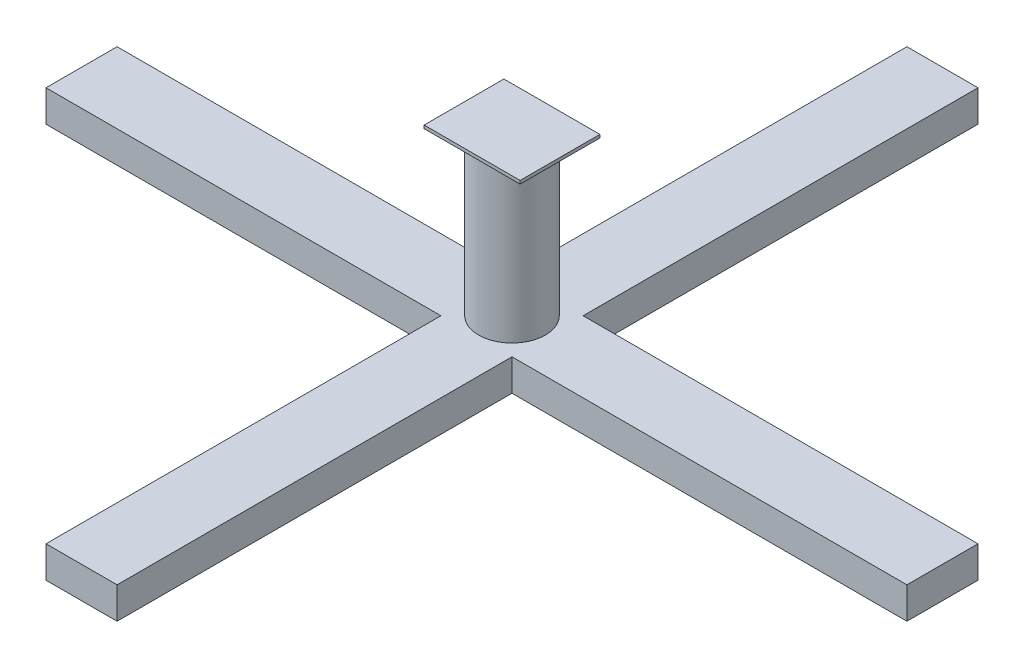
SolidWorks part; units mm, degrees
ref_plane "Alzado" through (0, 0, 0) normal (0, 0, 1) x (1, 0, 0)
ref_plane "Planta" through (0, 0, 0) normal (0, 1, 0) x (1, 0, 0)
ref_plane "Vista lateral" through (0, 0, 0) normal (1, 0, 0) x (0, 0, -1)
sketch "Croquis1" plane through (0, 0, 0) normal (0, 1, 0) x (1, 0, 0)
  line L0 (45, 0) -> (545, 0)
  line L1 (-45, 0) -> (-545, 0)
  line L2 (0, 45) -> (-545, 45)
  line L3 (-545, 0) -> (-545, 45)
  line L4 (0, 45) -> (545, 45)
  line L5 (545, 45) -> (545, 0)
  line L6 (0, -45) -> (545, -45)
  line L7 (545, -45) -> (545, 0)
  line L8 (0, -45) -> (-545, -45)
  line L9 (-545, -45) -> (-545, 0)
  line L10 (0, -45) -> (0, -545)
  line L11 (-45, 0) -> (-45, -545)
  line L12 (-45, -545) -> (0, -545)
  line L13 (45, 0) -> (45, -545)
  line L14 (45, -545) -> (0, -545)
  line L15 (0, 45) -> (0, 545)
  line L16 (-45, 0) -> (-45, 545)
  line L17 (-45, 545) -> (0, 545)
  line L18 (45, 0) -> (45, 545)
  line L19 (45, 545) -> (0, 545)
  circle A0 centre (0, 0) radius 45
  dimension "D1" = 90
  dimension "D2" = 500
  dimension "D3" = 500
  dimension "D4" = 500
  dimension "D5" = 500
extrude "Saliente-Extruir1" add sketch "Croquis1" along normal blind 40 contours L14 L13 L6 L10 | L11 L12 L10 L8 | L0 L13 L6 L7 | L18 L0 L5 L4 | L1 L16 L2 L3 | L11 L1 L9 L8 | A0 L11 L8 | A0 L18 L4 | A0 L2 L16 | L17 L16 L2 L15 | L18 L19 L15 L4 | A0 L6 L13 | A0 region at (295, 0, -22.5) region at (295, 0, 22.5) region at (34.9484, 0, -34.9484) region at (0, 0, 0) region at (34.9484, 0, 34.9484) region at (22.5, 0, 295) region at (22.5, 0, -295) region at (-34.9484, 0, -34.9484) region at (-22.5, 0, -295) region at (-22.5, 0, 295) region at (-34.9484, 0, 34.9484) region at (-295, 0, -22.5) region at (-295, 0, 22.5)
sketch "Croquis2" plane through (0, 40, 0) normal (0, 1, 0) x (1, 0, 0)
  circle A0 centre (0, 0) radius 42.35
  dimension "D1" = 84.7
extrude "Saliente-Extruir2" add sketch "Croquis2" along normal blind 200
sketch "Croquis3" plane through (0, 240, 0) normal (0, 1, 0) x (1, 0, 0)
  circle A0 centre (0, 0) radius 39.35
  circle A1 centre (0, 0) radius 42.35 construction
  dimension "D1" = 3
extrude "Cortar-Extruir1" cut sketch "Croquis3" against normal up to surface (200 mm away) up to face at (0, 40, 42.35)
sketch "Croquis4" plane through (0, 240, 0) normal (0, 1, 0) x (1, 0, 0)
  circle A0 centre (0, 0) radius 39.35
  circle A1 centre (0, 0) radius 36.35
  circle A2 centre (0, 0) radius 39.35 construction
  dimension "D1" = 3
extrude "Saliente-Extruir3" add sketch "Croquis4" against normal up to surface (200 mm away) and the other way blind 4 up to face at (0, 40, 42.35)
sketch "Croquis6" plane through (0, 240, 0) normal (0, 1, 0) x (1, 0, 0)
  line L1 (-60.75, -50.5) -> (60.75, -50.5)
  line L2 (-60.75, -50.5) -> (-60.75, 50.5)
  line L3 (-60.75, 50.5) -> (60.75, 50.5)
  line L4 (60.75, -50.5) -> (60.75, 50.5)
  point P0 (0, 0)
  dimension "D1" = 121.5
  dimension "D2" = 101
extrude "Saliente-Extruir4" add sketch "Croquis6" along normal blind 4
